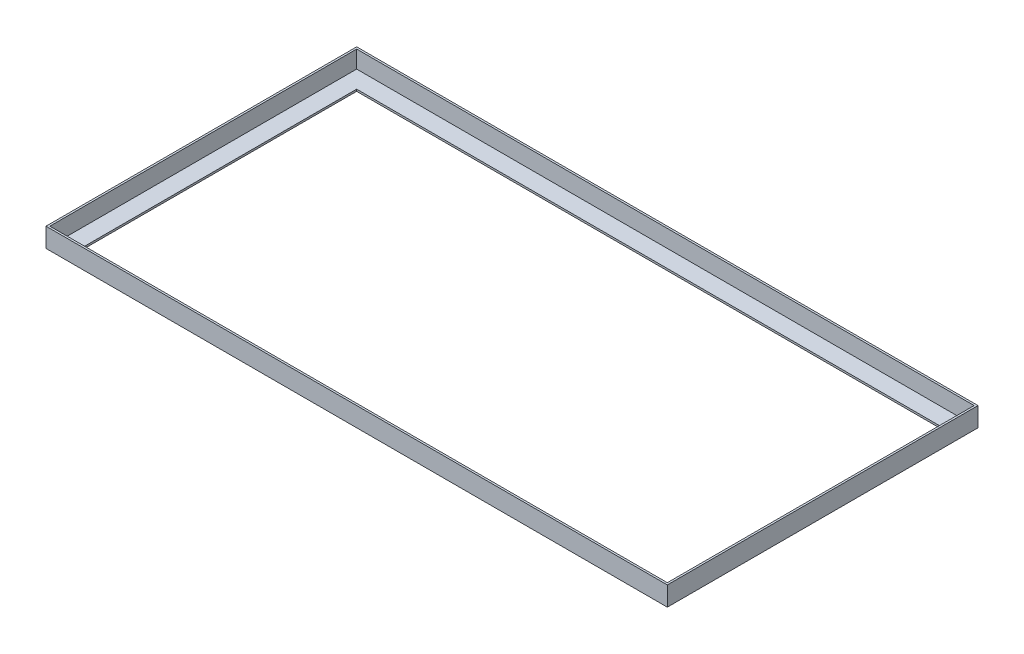
SolidWorks part; units mm, degrees
ref_plane "Спереди" through (0, 0, 0) normal (0, 0, 1) x (1, 0, 0)
ref_plane "Сверху" through (0, 0, 0) normal (0, 1, 0) x (1, 0, 0)
ref_plane "Справа" through (0, 0, 0) normal (1, 0, 0) x (0, 0, -1)
sketch "Эскиз1" plane through (0, 0, 0) normal (0, 1, 0) x (1, 0, 0)
  line L1 (-111.8182, 726.656) -> (1498.1818, 726.656)
  line L2 (-111.8182, 726.656) -> (-111.8182, -78.344)
  line L3 (-111.8182, -78.344) -> (1498.1818, -78.344)
  line L4 (1498.1818, 726.656) -> (1498.1818, -78.344)
  line L5 (-106.8182, 721.656) -> (1493.1818, 721.656)
  line L6 (-106.8182, 721.656) -> (-106.8182, -73.344)
  line L7 (-106.8182, -73.344) -> (1493.1818, -73.344)
  line L8 (1493.1818, 721.656) -> (1493.1818, -73.344)
  line L13 (-61.8182, 676.656) -> (1448.1818, 676.656)
  line L14 (-61.8182, 676.656) -> (-61.8182, -28.344)
  line L15 (-61.8182, -28.344) -> (1448.1818, -28.344)
  line L16 (1448.1818, 676.656) -> (1448.1818, -28.344)
  dimension "D1" = 5
  dimension "D2" = 5
  dimension "D3" = 5
  dimension "D4" = 5
  dimension "D5" = 45
  dimension "D6" = 45
  dimension "D7" = 45
  dimension "D8" = 45
  dimension "D9" = 805
  dimension "D10" = 1610
extrude "Бобышка-Вытянуть1" add sketch "Эскиз1" along normal blind 50 contours L4 L1 L2 L3 L5 L8 L7 L6 region at (693.1818, 0, -724.856)
ref_plane "Плоскость4" through (1493.1818, 0, -721.656) normal (1, 0, 0) x (0, 0, -1)
extrude "Бобышка-Вытянуть2" add sketch "Эскиз1<7>" along normal blind 5 contours L8 L5 L6 L7 L13 L16 L15 L14 region at (693.1818, 0, -703.7898)
sketch "Эскиз1<7>" plane through (0, 0, 0) normal (0, 1, 0) x (1, 0, 0) same geometry as "Эскиз1"
ref_plane "Плоскость13" through (-106.8182, 5, -721.656) normal (0, -1, 0) x (-1, 0, 0)
